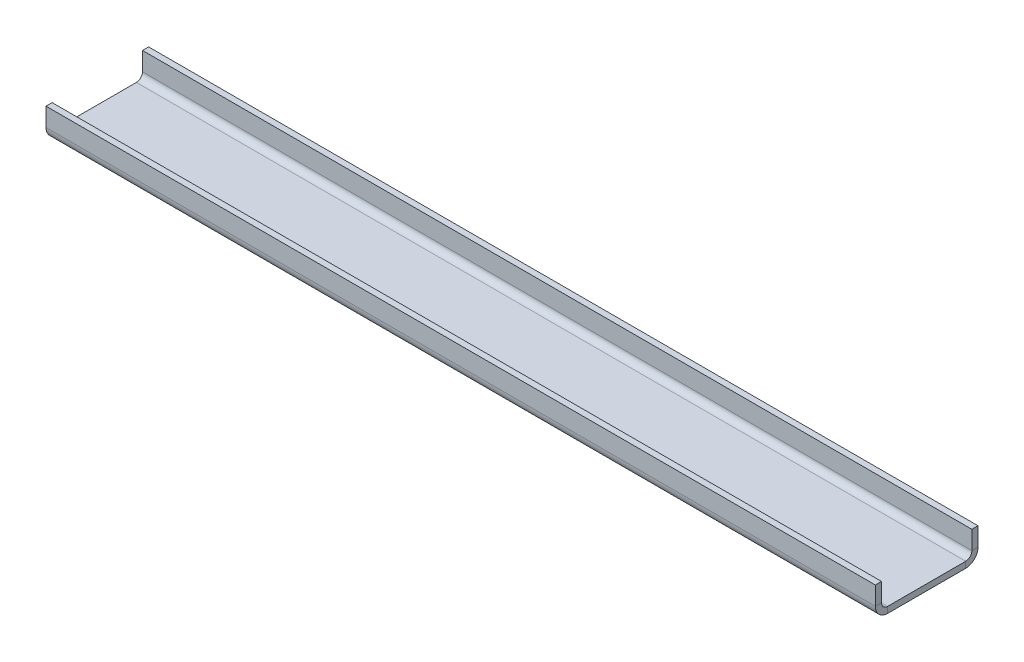
SolidWorks part; units mm, degrees
note: The reader was unsure of these and kept them because the rebuilt part matched: flange length of "Tôle pliée sur arête1".
ref_plane "Plan de face" through (0, 0, 0) normal (0, 0, 1) x (1, 0, 0)
ref_plane "Plan de dessus" through (0, 0, 0) normal (0, 1, 0) x (1, 0, 0)
ref_plane "Plan de droite" through (0, 0, 0) normal (1, 0, 0) x (0, 0, -1)
sketch "Esquisse2" plane through (0, 0, 0) normal (0, 1, 0) x (1, 0, 0)
  line L1 (0, 0) -> (404, 0)
  line L2 (0, 0) -> (0, 50)
  line L3 (0, 50) -> (404, 50)
  line L4 (404, 0) -> (404, 50)
  dimension "D1" = 50
  dimension "D2" = 404
sheet metal parameters "Tôlerie 1" thickness 3 parameters "D1"=3
base flange "Tôle de base pliée1" sketch "Esquisse2" thickness 3 reverse thickness direction no parameters "D1"=3
edge flange "Tôle pliée sur arête1" sketch "Esquisse7" flange profiles "Esquisse7", "Esquisse9" flange angle 90 flange length 15 flange position material inside bend radius 3 thickness 3 relief rectangular parameters "D6"=10, "D8"=1
sketch "Esquisse7" plane through (0, 0, 0) normal (0, 0, 1) x (1, 0, 0)
  line L0 (0, 0) -> (404, 0) construction
  line L1 (0, 0) -> (404, 0)
  line L2 (0, 0) -> (0, 12)
  line L3 (0, 12) -> (404, 12)
  line L4 (404, 12) -> (404, 0)
sketch "Esquisse9" plane through (0, 0, -50) normal (0, 0, -1) x (-1, 0, 0)
  line L0 (-404, 0) -> (0, 0) construction
  line L1 (-404, 0) -> (0, 0)
  line L2 (-404, 0) -> (-404, 12)
  line L3 (-404, 12) -> (0, 12)
  line L4 (0, 12) -> (0, 0)
bend "Pli d'arête1" bend radius 3 bend angle 90 parameters "D5"=1
bend "Pli d'arête2" bend radius 3 bend angle 90 parameters "D5"=2
flat pattern "Etat déplié1" [suppressed]
sketch "Lignes de pliage1" plane through (0, 0, 0) normal (0, 1, 0) x (1, 0, 0)
sketch3d "Cube de visualisation1" [suppressed]
  line L0 (-650, 50, 0) -> (0, 50, 0) construction
  line L1 (-650, 0, 0) -> (0, 0, 0) construction
  line L2 (-650, 50, 0) -> (-650, 0, 0) construction
  line L3 (0, 50, 0) -> (0, 0, 0) construction
bend of the flat pattern "Dépliage-<Pli d'arête1>1"
bend of the flat pattern "Dépliage-<Pli d'arête2>1"
